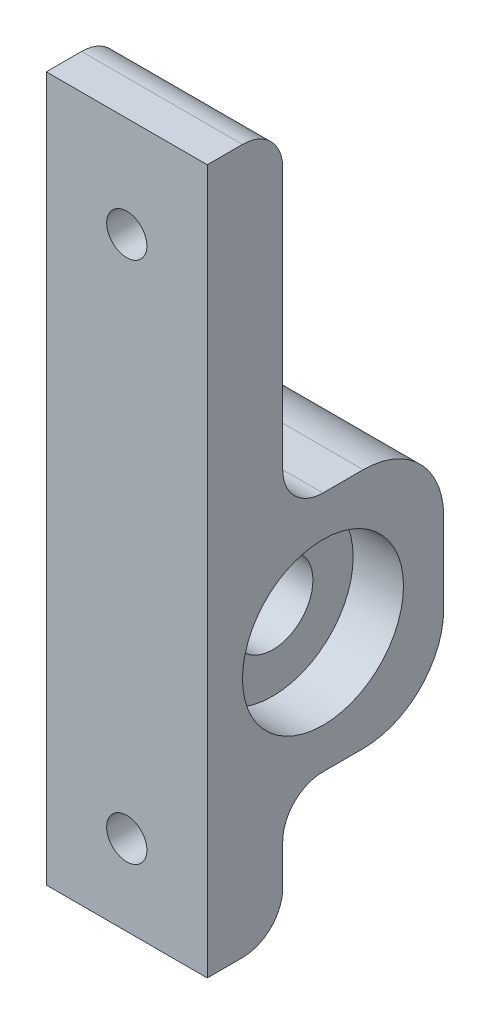
SolidWorks part; units mm, degrees
ref_plane "Plan de face" through (0, 0, 0) normal (0, 0, 1) x (1, 0, 0)
ref_plane "Plan de dessus" through (0, 0, 0) normal (0, 1, 0) x (1, 0, 0)
ref_plane "Plan de droite" through (0, 0, 0) normal (1, 0, 0) x (0, 0, -1)
sketch "Esquisse1" plane through (0, 0, 0) normal (0, 0, 1) x (1, 0, 0)
  line L0 (0, 0) -> (16, 0)
  line L1 (0, 0) -> (0, 70)
  line L2 (16, 0) -> (16, 70)
  line L3 (0, 70) -> (16, 70)
extrude "Boss.-Extru.1" add sketch "Esquisse1" along normal blind 7.5
sketch "Esquisse2" plane through (0, 0, 0) normal (0, 0, -1) x (-1, 0, 0)
  line L0 (0, 0) -> (-16, 0)
  line L1 (0, 0) -> (0, 12)
  line L2 (-16, 0) -> (-16, 12)
  line L3 (0, 12) -> (-16, 12)
  line L4 (0, 12) -> (-16, 12)
  line L5 (0, 12) -> (0, 36)
  line L6 (-16, 12) -> (-16, 36)
  line L7 (0, 36) -> (-16, 36)
  line M1 (0, 0) -> (0, 70)
  line M3 (-16, 70) -> (-16, 0)
extrude "Boss.-Extru.2" add sketch "Esquisse2" along normal blind 16 contours L7 L3 M1 M3 region at (8, 24, 0)
sketch "Esquisse3" plane through (0, 0, 0) normal (0, 0, -1) x (-1, 0, 0)
  line L0 (-16, 70) -> (-8, 70)
  line L1 (-16, 70) -> (-16, 60)
  line L2 (-8, 70) -> (-8, 60)
  line L3 (-16, 60) -> (-8, 60)
  line L4 (-16, 70) -> (0, 70) construction
  circle A0 centre (-8, 60) radius 2
  circle A1 centre (-8, 60) radius 3.5
extrude "Enlèv. mat.-Extru.1" cut sketch "Esquisse3" against normal through all contours L3 A0 L2 | L2 A0 L3 region at (7.7171, 59.7171, 0) region at (8.8488, 60.8488, 0)
extrude "Enlèv. mat.-Extru.2" cut sketch "Esquisse3<4>" against normal blind 3.5 contours L3 A1 L2 A0 | L2 A1 L3 A0 region at (5.5951, 62.4049, 0) region at (9.7941, 61.7941, 0)
sketch "Esquisse3<4>" plane through (0, 0, 0) normal (0, 0, -1) x (-1, 0, 0) same geometry as "Esquisse3"
sketch "Esquisse4" plane through (0, 0, 0) normal (0, 0, -1) x (-1, 0, 0)
  line L0 (0, 0) -> (-8, 0)
  line L1 (0, 0) -> (0, 8)
  line L2 (-8, 0) -> (-8, 8)
  line L3 (0, 8) -> (-8, 8)
  line L4 (0, 0) -> (-16, 0) construction
  circle A0 centre (-8, 8) radius 3.5
  circle A1 centre (-8, 8) radius 2
extrude "Enlèv. mat.-Extru.3" cut sketch "Esquisse4" against normal through all contours L3 A1 L2 | L2 A1 L3 region at (8.2829, 8.2829, 0) region at (7.1512, 7.1512, 0)
extrude "Enlèv. mat.-Extru.4" cut sketch "Esquisse4<3>" against normal blind 3.5 contours A1 L2 A0 L3 | A1 L3 A0 L2 region at (10.4049, 10.4049, 0) region at (6.2059, 6.2059, 0)
sketch "Esquisse4<3>" plane through (0, 0, 0) normal (0, 0, -1) x (-1, 0, 0) same geometry as "Esquisse4"
sketch "Esquisse5" plane through (16, 0, 0) normal (1, 0, 0) x (0, 0, -1)
  line L0 (16, 12) -> (16, 24)
  line L1 (16, 12) -> (4, 12)
  line L2 (16, 24) -> (4, 24)
  line L3 (4, 12) -> (4, 24)
  line L4 (16, 36) -> (16, 12) construction
  circle A0 centre (4, 24) radius 4
  circle A1 centre (4, 24) radius 8
extrude "Enlèv. mat.-Extru.5" cut sketch "Esquisse5" against normal through all contours L3 A0 L2 | L2 A0 L3 region at (16, 22.3023, -5.6977) region at (16, 24.5659, -3.4341)
extrude "Enlèv. mat.-Extru.6" cut sketch "Esquisse5<3>" against normal blind 5 contours L3 A1 L2 A0 | L2 A1 L3 A0 region at (16, 20.0388, -7.9612) region at (16, 24.2263, -10)
sketch "Esquisse5<3>" plane through (16, 0, 0) normal (1, 0, 0) x (0, 0, -1) same geometry as "Esquisse5"
fillet "Congé1" radius 4 4 edges at (8, 70, 0) (8, 0, 0)
fillet "Congé2" radius 8 2 edges at (8, 36, -16) (8, 12, -16)
